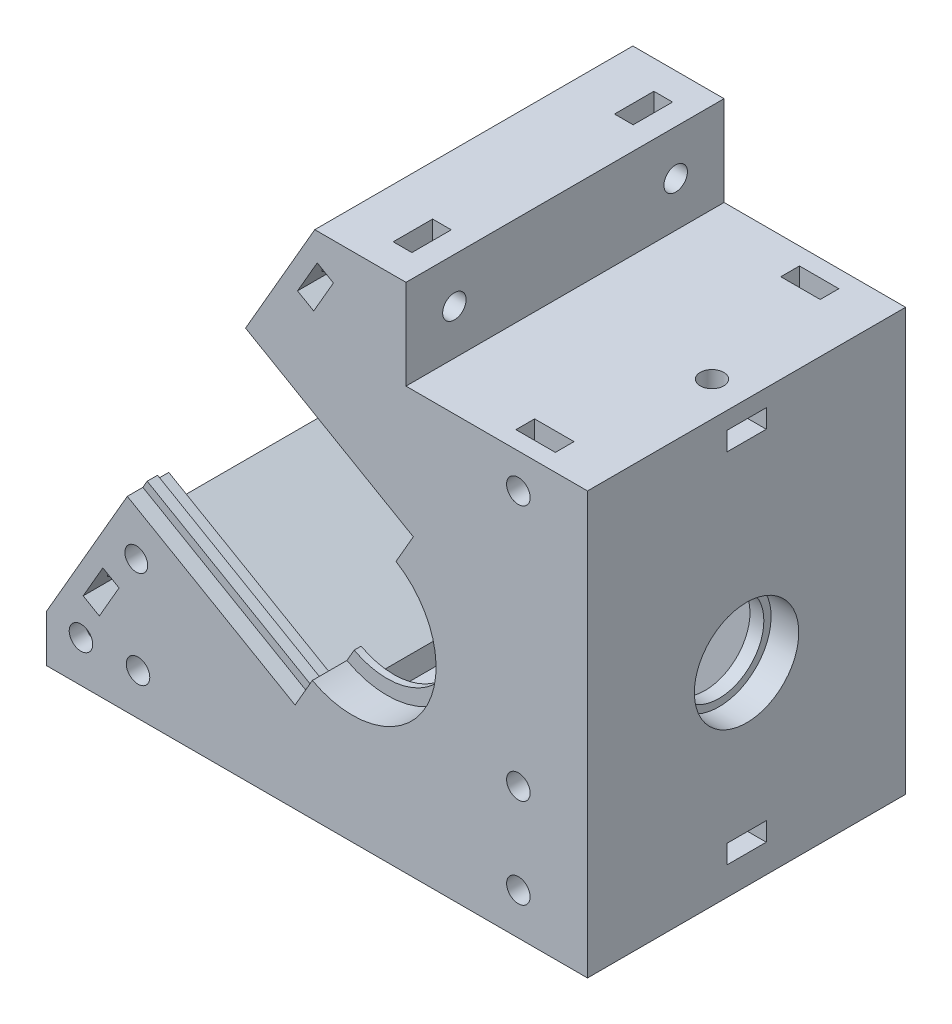
SolidWorks part; units mm, degrees
material "ABS"
ref_plane "Front Plane" through (0, 0, 0) normal (0, 0, 1) x (1, 0, 0)
ref_plane "Top Plane" through (0, 0, 0) normal (0, 1, 0) x (1, 0, 0)
ref_plane "Right Plane" through (0, 0, 0) normal (1, 0, 0) x (0, 0, -1)
sketch "Sketch1" plane through (0, 0, 0) normal (0, 0, 1) x (1, 0, 0)
  line L0 (-14, -24.2487) -> (-38, -10.3923)
  line L1 (-38, 33) -> (34, 33)
  line L2 (-38, 33) -> (-38, -31)
  line L3 (-38, -31) -> (34, -31)
  line L4 (34, 33) -> (34, -31)
  line L7 (-15, -31) -> (-15, -27.5)
  line L8 (-15, -27.5) -> (15, -27.5)
  line L9 (15, -27.5) -> (15, -31)
  line L16 (14, 24.2487) -> (-10, 38.1051)
  line L17 (7.75, 33) -> (7.75, 46)
  line L18 (7.75, 46) -> (-5.25, 46)
  line L19 (28, 10) -> (28, -10)
  line L20 (28, 10) -> (28, 14)
  line L21 (28, 14) -> (16.8, 22.4)
  line L22 (-38, -10.3923) -> (-5.4419, 46)
  line L23 (-5.4419, 46) -> (-5.25, 46)
  line L24 (-38, -10.3923) -> (-44.25, -21.2176)
  line L25 (-44.25, -21.2176) -> (-44.25, -31)
  line L26 (-44.25, -31) -> (-38, -31)
  line L27 (-44.25, -21.2176) -> (-44.25, -15.2176) construction
  line L28 (-44.25, -15.2176) -> (-8.906, 46) construction
  line L29 (-8.906, 46) -> (-5.4419, 46) construction
  line L30 (-10, 38.1051) -> (-12.5981, 39.6051) construction
  line L31 (-38, -10.3923) -> (-40.5981, -8.8923) construction
  line L32 (28, -10) -> (28, -14)
  line L33 (28, -14) -> (16.8, -22.4)
  circle A0 centre (0, 0) radius 28
  circle A1 centre (0, 0) radius 12.1
  circle A2 centre (0, 0) radius 10
  point P22 (28, 0)
  dimension "D1" = 56
  dimension "D2" = 24.2
  dimension "D3" = 20
  dimension "D4" = 34
  dimension "D6" = 3.5
  dimension "D7" = 15
  dimension "D8" = 15
  dimension "D10" = 38
  dimension "D5" = 33
  dimension "D9" = 31
  dimension "D11" = 30
  dimension "D12" = 7.75
  dimension "D13" = 13
  dimension "D14" = 13
  dimension "D15" = 20
  dimension "D16" = 9.1162
  dimension "D17" = 12.5
  dimension "D18" = 3
  dimension "D19" = 7.3038
  dimension "D20" = 7.3842
  dimension "D21" = 4
  dimension "D22" = 4
extrude "Boss-Extrude1" add sketch "Sketch1" along normal blind 6 contours A0 L20 L19 L8 L9 L3 L4 L1 L16 | A0 L0 L2 L3 L7 L8 | L25 L26 L2 L24 | L23 L22 L16 L1 L17 L18 | A0 L22 L0 | L22 A0 L8 A1 | A0 L16 L1 L22 | L22 L1 L16 | A0 L19 L20 | A0 L19 region at (-27.5845, -23.6186, 0) region at (-29.6112, -8.3492, 0) region at (-25.7125, -8.9071, 0) region at (-40.7539, -23.0811, 0) region at (-7.4692, 28.6958, 0) region at (11.6201, -26.2754, 0) region at (-8.035, 34.7017, 0) region at (25.6746, -12.8373, 0) region at (0.2743, 39.7035, 0) region at (25.6746, 12.8373, 0)
extrude "Boss-Extrude2" add sketch "Sketch1<3>" along normal blind 40 contours A0 L20 L19 L8 L9 L3 L4 L1 L16 | L23 L22 L16 L1 L17 L18 | A0 L0 L2 L3 L7 L8 | L25 L26 L2 L24 region at (-27.5845, -23.6186, 0) region at (-40.7539, -23.0811, 0) region at (11.6201, -26.2754, 0) region at (0.2743, 39.7035, 0)
sketch "Sketch1<3>" plane through (0, 0, 0) normal (0, 0, 1) x (1, 0, 0) same geometry as "Sketch1"
extrude "Boss-Extrude3" add sketch "Sketch1<4>" along normal blind 6 from surface contours A0 L20 L19 L8 L9 L3 L4 L1 L16 | L22 A0 L8 A1 | A0 L19 L20 | A0 L19 | A0 L0 L2 L3 L7 L8 | A0 L22 L0 | A0 L16 L1 L22 | L22 L1 L16 | L23 L22 L16 L1 L17 L18 | L25 L26 L2 L24 region at (-27.5845, -23.6186, 0) region at (-29.6112, -8.3492, 0) region at (-25.7125, -8.9071, 0) region at (-40.7539, -23.0811, 0) region at (-7.4692, 28.6958, 0) region at (11.6201, -26.2754, 0) region at (-8.035, 34.7017, 0) region at (25.6746, -12.8373, 0) region at (0.2743, 39.7035, 0) region at (25.6746, 12.8373, 0) starting at face at (14.8032, 7.3384, 40)
sketch "Sketch1<4>" plane through (0, 0, 0) normal (0, 0, 1) x (1, 0, 0) same geometry as "Sketch1"
extrude "Boss-Extrude4" add sketch "Sketch1<5>" against normal blind 1 from surface contours A1 A2 region at (-11.7578, 0, 0) starting at face at (4.1782, -2.8269, 6)
sketch "Sketch1<5>" plane through (0, 0, 0) normal (0, 0, 1) x (1, 0, 0) same geometry as "Sketch1"
extrude "Boss-Extrude5" add sketch "Sketch1<6>" along normal blind 1 from surface contours A1 A2 region at (-11.7578, 0, 0) starting at face at (4.1782, -2.8269, 40)
sketch "Sketch1<6>" plane through (0, 0, 0) normal (0, 0, 1) x (1, 0, 0) same geometry as "Sketch1"
sketch "Sketch2" plane through (0, -27.5, 0) normal (0, -1, 0) x (1, 0, 0)
  line L0 (15, 46) -> (15, 0) construction
  line L1 (15, 40) -> (-15, 40)
  line L2 (15, 40) -> (15, 6)
  line L3 (15, 6) -> (-15, 6)
  line L4 (-15, 40) -> (-15, 6)
  line L5 (-15, 46) -> (-15, 0) construction
  line L6 (-5.2678, 6) -> (5.2678, 6) construction
  line L7 (5.2678, 40) -> (-5.2678, 40) construction
sketch "Sketch3" plane through (0, 0, 0) normal (0, 0, -1) x (-1, 0, 0)
  line L0 (-6.05, 10.4789) -> (17.95, 24.3353)
  line L1 (44.25, -21.2176) -> (5.4419, 46) construction
  line L2 (6.05, -10.4789) -> (30.05, 3.3775)
  line L3 (-8.55, 14.809) -> (15.45, 28.6654)
  line L4 (8.2902, -14.959) -> (32.55, -0.9526)
  line L5 (6.05, -10.4789) -> (30.05, 3.3775) construction
  line L6 (-8.55, 14.809) -> (-6.05, 10.4789)
  line L7 (8.55, -14.809) -> (6.05, -10.4789)
  line L8 (-6.05, 10.4789) -> (6.05, -10.4789)
  line L9 (-8.55, 14.809) -> (-8.8098, 14.659)
  line L10 (-8.8098, 14.659) -> (8.2902, -14.959)
  line L11 (8.55, -14.809) -> (32.55, -0.9526) construction
  circle A0 centre (0, 0) radius 12.1 construction
  line M11 (44.25, -21.2176) -> (5.4419, 46)
  circle M17 centre (0, 0) radius 12.1
  dimension "D1" = 90
  dimension "D2" = 90
  dimension "D5" = 90
  dimension "D6" = 0.3
  dimension "D7" = 27.7128
  dimension "D3" = 5
  dimension "D4" = 5
extrude "Cut-Extrude1" cut sketch "Sketch2" against normal blind 10
extrude "Cut-Extrude2" cut sketch "Sketch3" against normal blind 49 contours L3 L6 L0 M11 | L2 L0 M17 M11 | L8 M17 | L9 L10 L6 M17 | L10 L8 M17 | L7 L4 L2 M11 | L10 L4 L7 M17 region at (-4.7, 19.5722, 0) region at (7.4296, 12.5684, 0) region at (-4.4474, 2.5677, 0) region at (-15.9416, 9.2039, 0) region at (0.1299, -0.075, 0) region at (-19.3, -5.7158, 0) region at (-7.1698, -12.7184, 0)
sketch "Sketch4" plane through (0.2598, -0.15, 0) normal (-0.866, 0.5, 0) x (0, 0, 1)
  line L0 (6, 17.1) -> (0, 17.1) construction
  line L1 (2.25, 17.1) -> (3.75, 17.1)
  line L2 (2.25, 17.1) -> (2.25, 15.85)
  line L3 (2.25, 15.85) -> (3.75, 15.85)
  line L4 (3.75, 17.1) -> (3.75, 15.85)
  line L5 (42.25, 17.1) -> (43.75, 17.1)
  line L6 (42.25, 17.1) -> (42.25, 15.85)
  line L7 (42.25, 15.85) -> (43.75, 15.85)
  line L8 (43.75, 17.1) -> (43.75, 15.85)
  line L9 (46, 17.1) -> (40, 17.1) construction
  line L10 (2.25, -15.85) -> (3.75, -15.85)
  line L11 (2.25, -15.85) -> (2.25, -17.1)
  line L12 (2.25, -17.1) -> (3.75, -17.1)
  line L13 (3.75, -15.85) -> (3.75, -17.1)
  line L14 (42.25, -15.85) -> (43.75, -15.85)
  line L15 (42.25, -15.85) -> (42.25, -17.1)
  line L16 (42.25, -17.1) -> (43.75, -17.1)
  line L17 (43.75, -15.85) -> (43.75, -17.1)
  line L18 (6, -17.1) -> (0, -17.1) construction
  line L19 (46, -17.1) -> (40, -17.1) construction
  point P6 (3, 17.1)
  point P7 (3, 17.1)
  point P12 (43, 17.1)
  point P15 (43, 17.1)
  point P28 (3, -17.1)
  point P29 (3, -17.1)
  point P30 (43, -17.1)
  point P33 (43, -17.1)
  dimension "D1" = 1.5
  dimension "D2" = 1.25
  dimension "D3" = 1.5
  dimension "D4" = 1.25
  dimension "D5" = 1.5
  dimension "D6" = 1.25
  dimension "D7" = 1.5
  dimension "D8" = 1.25
extrude "Boss-Extrude6" add sketch "Sketch4" along normal up to surface (28.0128 mm away) up to face at (-11.5855, 35.359, 23)
sketch "Sketch5" plane through (28, 0, 0) normal (-1, 0, 0) x (0, 0, 1)
  line L0 (40, 14) -> (6, -14) construction
  circle A0 centre (23, 0) radius 7.55
  circle A1 centre (23, 0) radius 6.5
  point P7 (23, 0)
  dimension "D1" = 15.1
  dimension "D2" = 13
extrude "Cut-Extrude3" cut sketch "Sketch5" against normal blind 49 contours A1 L0 | L0 A1 region at (28, -2.1295, 24.7537) region at (28, 2.1295, 21.2463)
extrude "Cut-Extrude4" cut sketch "Sketch5<3>" along normal blind 4 from surface contours L0 A0 A1 | A0 L0 A1 region at (28, 2.4881, 29.9351) region at (28, 4.6064, 28.3071) starting at face at (34, 6.5, 23)
sketch "Sketch5<3>" plane through (28, 0, 0) normal (-1, 0, 0) x (0, 0, 1) same geometry as "Sketch5"
sketch "Sketch6" plane through (-24, 13.8564, 0) normal (-0.866, 0.5, 0) x (0, 0, 1)
  line L0 (40, -28) -> (6, -28) construction
  line L1 (0, -40.5) -> (0, -17.1) construction
  line L2 (46, -17.1) -> (46, -40.5) construction
  line L3 (40, 28) -> (6, 28) construction
  line L5 (46, -40.5) -> (0, -40.5) construction
  circle A0 centre (4, -31) radius 1.7
  circle A1 centre (42, -31) radius 1.7
  circle A2 centre (42, 31) radius 1.7
  circle A3 centre (4, 31) radius 1.7
  dimension "D1" = 3.4
  dimension "D2" = 3.4
  dimension "D3" = 3.4
  dimension "D4" = 3.4
  dimension "D5" = 3
  dimension "D6" = 4
  dimension "D7" = 4
  dimension "D8" = 3
  dimension "D9" = 9.5
  dimension "D10" = 62
  dimension "D11" = 38
extrude "Cut-Extrude5" cut sketch "Sketch6" against normal blind 8
sketch "Sketch7" plane through (0, 0, 46) normal (0, 0, 1) x (1, 0, 0)
  line L0 (34, -31) -> (34, 33) construction
  line L1 (-44.25, -31) -> (34, -31)
  line L2 (-44.25, -31) -> (-44.25, -27)
  line L3 (-44.25, -27) -> (34, -27)
  line L4 (34, -31) -> (34, -27)
  line L6 (15, -27.5) -> (-15, -27.5) construction
  dimension "D1" = 0.5
extrude "Cut-Extrude6" cut sketch "Sketch7" against normal blind 64
sketch "Sketch8" plane through (0, 0, 46) normal (0, 0, 1) x (1, 0, 0)
  line L0 (34, -27) -> (-44.25, -27) construction
  line L1 (-44.25, -27) -> (-44.25, -21.2176) construction
  line L2 (34, -27) -> (34, 33) construction
  circle A0 centre (-39.25, -22) radius 1.7
  circle A1 centre (29, -22) radius 1.7
  dimension "D1" = 3.4
  dimension "D2" = 3.4
  dimension "D3" = 5
  dimension "D4" = 5
  dimension "D5" = 5
  dimension "D6" = 5
extrude "Cut-Extrude7" cut sketch "Sketch8" against normal blind 10 contours A0 region at (-39.25, -22, 46)
extrude "Cut-Extrude9" cut sketch "Sketch8<2>" along normal blind 10 from surface contours A0 region at (-39.25, -22, 46) starting at face at (-3.6295, 7.9996, 0)
sketch "Sketch8<2>" plane through (0, 0, 46) normal (0, 0, 1) x (1, 0, 0) same geometry as "Sketch8"
sketch "Sketch10" plane through (-44.25, 0, 0) normal (-1, 0, 0) x (0, 0, 1)
  line L0 (0, -27) -> (46, -27) construction
  line L1 (20.15, -21.2176) -> (25.85, -21.2176)
  line L2 (20.15, -21.2176) -> (20.15, -23.9176)
  line L3 (20.15, -23.9176) -> (25.85, -23.9176)
  line L4 (25.85, -21.2176) -> (25.85, -23.9176)
  line L5 (20.15, -21.2176) -> (25.85, -23.9176) construction
  line L6 (20.15, -23.9176) -> (25.85, -21.2176) construction
  line L7 (46, -21.2176) -> (0, -21.2176) construction
  point P0 (23, -22.5676)
  point P8 (23, -27)
  dimension "D1" = 5.7
  dimension "D2" = 2.7
extrude "Cut-Extrude10" cut sketch "Sketch10" against normal blind 8.5
sketch "Sketch11" plane through (34, 0, 0) normal (1, 0, 0) x (0, 0, -1)
  line L0 (0, -27) -> (-46, -27) construction
  line L1 (-43.7, -24.85) -> (-41, -24.85)
  line L2 (-43.7, -24.85) -> (-43.7, -19.15)
  line L3 (-43.7, -19.15) -> (-41, -19.15)
  line L4 (-41, -24.85) -> (-41, -19.15)
  line L5 (-43.7, -24.85) -> (-41, -19.15) construction
  line L6 (-43.7, -19.15) -> (-41, -24.85) construction
  line L7 (-46, -27) -> (-46, 33) construction
  line L8 (-5, -24.85) -> (-2.5, -24.85)
  line L9 (-5, -24.85) -> (-5, -19.15)
  line L10 (-5, -19.15) -> (-2.5, -19.15)
  line L11 (-2.5, -24.85) -> (-2.5, -19.15)
  line L12 (-5, -24.85) -> (-2.5, -19.15) construction
  line L13 (-5, -19.15) -> (-2.5, -24.85) construction
  line L14 (0, 33) -> (0, -27) construction
  point P0 (-42.35, -22)
  point P9 (-3.75, -22)
  dimension "D1" = 5.7
  dimension "D2" = 2.7
  dimension "D3" = 5
  dimension "D4" = 5
  dimension "D5" = 5.7
  dimension "D6" = 2.5
  dimension "D7" = 5
extrude "Cut-Extrude12" cut sketch "Sketch11" along normal blind 8.5 from surface starting at face at (-44.25, -23.3382, 23)
extrude "Cut-Extrude13" cut sketch "Sketch10<2>" along normal blind 8.5 from surface starting at face at (34, 3, 23)
sketch "Sketch10<2>" plane through (-44.25, 0, 0) normal (-1, 0, 0) x (0, 0, 1) same geometry as "Sketch10"
sketch "Sketch12" plane through (0, 0, 46) normal (0, 0, 1) x (1, 0, 0)
  line L0 (-36.0831, -11.6722) -> (-38.9331, -16.6086)
  line L1 (-38.9331, -16.6086) -> (-36.5949, -17.9586)
  line L2 (-36.5949, -17.9586) -> (-33.7449, -13.0222)
  line L3 (-33.7449, -13.0222) -> (-36.0831, -11.6722)
  line L4 (-32.55, -0.9526) -> (-44.25, -21.2176) construction
  line L6 (-39.5, -12.9904) -> (-28.0908, -19.5775) construction
  line L7 (-5.0831, 42.0214) -> (-7.9331, 37.085)
  line L8 (-7.9331, 37.085) -> (-5.5949, 35.735)
  line L9 (-5.5949, 35.735) -> (-2.7449, 40.6714)
  line L10 (-2.7449, 40.6714) -> (-5.0831, 42.0214)
  point P6 (-37.5081, -14.1404)
  point P7 (-39.5, -12.9904)
  point P17 (-8.7952, 39.4691)
  dimension "D1" = 2.7
  dimension "D2" = 5.7
  dimension "D3" = 5
  dimension "D4" = 9.5
  dimension "D5" = 90
  dimension "D6" = 2.7
  dimension "D7" = 5.7
  dimension "D8" = 62
extrude "Cut-Extrude14" cut sketch "Sketch12" against normal blind 7.5
extrude "Cut-Extrude15" cut sketch "Sketch12<2>" along normal blind 7.5 from surface starting at face at (-37.55, -22, 0)
sketch "Sketch12<2>" plane through (0, 0, 46) normal (0, 0, 1) x (1, 0, 0) same geometry as "Sketch12"
sketch "Sketch13" plane through (7.75, 0, 0) normal (1, 0, 0) x (0, 0, -1)
  line L0 (-46, 46) -> (0, 46) construction
  line L1 (-46, 46) -> (0, 33) construction
  circle A0 centre (-39, 39.5) radius 1.7
  circle A1 centre (-7, 39.5) radius 1.7
  point P10 (-23, 39.5)
  dimension "D1" = 3.4
  dimension "D2" = 3.4
  dimension "D3" = 6.5
  dimension "D4" = 16
  dimension "D5" = 16
extrude "Cut-Extrude16" cut sketch "Sketch13" against normal blind 10
sketch "Sketch14" plane through (0, 46, 0) normal (0, 1, 0) x (1, 0, 0)
  line L0 (1.75, -9.85) -> (4.45, -9.85)
  line L1 (1.75, -41.85) -> (4.45, -41.85)
  line L2 (1.75, -41.85) -> (1.75, -36.15)
  line L3 (1.75, -36.15) -> (4.45, -36.15)
  line L4 (4.45, -41.85) -> (4.45, -36.15)
  line L5 (1.75, -41.85) -> (4.45, -36.15) construction
  line L6 (1.75, -36.15) -> (4.45, -41.85) construction
  line L7 (1.75, -9.85) -> (1.75, -4.15)
  line L8 (1.75, -4.15) -> (4.45, -4.15)
  line L9 (4.45, -9.85) -> (4.45, -4.15)
  line L10 (1.75, -9.85) -> (4.45, -4.15) construction
  line L11 (1.75, -4.15) -> (4.45, -9.85) construction
  line L12 (7.75, -46) -> (7.75, 0) construction
  point P0 (3.1, -39)
  point P5 (3.1, -7)
  point P13 (7.75, -23)
  dimension "D1" = 2.7
  dimension "D2" = 5.7
  dimension "D3" = 2.7
  dimension "D4" = 5.7
  dimension "D5" = 6
  dimension "D6" = 16
  dimension "D7" = 16
extrude "Cut-Extrude17" cut sketch "Sketch14" against normal blind 10
sketch "Sketch15" plane through (0, 0, 46) normal (0, 0, 1) x (1, 0, 0)
  line L0 (0, 30.9475) -> (0, -37.7326) construction
  line L1 (0, 0) -> (-6.3411, -23.6652) construction
  line L2 (34, -27) -> (-44.25, -27) construction
  line L3 (0, 0) -> (6.3411, 23.6652) construction
  line L4 (34, 33) -> (7.75, 33) construction
  line L5 (-6.3411, -23.6652) -> (-16.7248, -20.8829) construction
  line L6 (-6.3411, -23.6652) -> (4.0426, -26.4475) construction
  line L7 (-16.7248, -20.8829) -> (-24.6937, -18.7476) construction
  line L8 (-24.6937, -18.7476) -> (-2.694, 63.3561) construction
  dimension "D1" = 15
  dimension "D2" = 24.5
  dimension "D3" = 44.25
  dimension "D4" = 34
  dimension "D5" = 27
  dimension "D6" = 15
  dimension "D7" = 24.5
  dimension "D8" = 1.4089
  dimension "D9" = 9.3348
  dimension "D10" = 40.3411
  dimension "D11" = 3.3348
  dimension "D12" = 10.75
  dimension "D13" = 10.75
  dimension "D14" = 8.25
  dimension "D15" = 85
  dimension "D16" = 17.3561
  dimension "D17" = 10.444
  dimension "D18" = 14.5802
sketch "Sketch17" plane through (0, 0, 46) normal (0, 0, 1) x (1, 0, 0)
  line L0 (34, -27) -> (-44.25, -27) construction
  circle A0 centre (-31, -22) radius 1.7
  circle A1 centre (24, -22) radius 1.7
  dimension "D2" = 3.4
  dimension "D3" = 3.4
  dimension "D1" = 5
  dimension "D4" = 31
  dimension "D5" = 24
extrude "Cut-Extrude19" cut sketch "Sketch17" against normal blind 20
extrude "Cut-Extrude20" cut sketch "Sketch17<2>" along normal blind 20 from surface starting at face at (-5.339, 38.8782, 0)
sketch "Sketch17<2>" plane through (0, 0, 46) normal (0, 0, 1) x (1, 0, 0) same geometry as "Sketch17"
sketch "Sketch19" plane through (0, -27, 0) normal (0, -1, 0) x (1, 0, 0)
  line L1 (-44.25, 46) -> (34, 46)
  line L2 (-44.25, 46) -> (-44.25, 0)
  line L3 (-44.25, 0) -> (34, 0)
  line L4 (34, 46) -> (34, 0)
extrude "Boss-Extrude7" add sketch "Sketch19" along normal blind 1
sketch "Sketch9" plane through (0, -28, 0) normal (0, -1, 0) x (1, 0, 0)
  line L1 (-44.25, 46) -> (34, 0) construction
  line L3 (-44.25, 46) -> (-44.25, 0) construction
  line L4 (34, 0) -> (34, 46) construction
  circle A0 centre (-39.25, 23) radius 1.7
  circle A1 centre (29, 23) radius 1.7
  point P10 (-5.125, 23)
  dimension "D1" = 3.4
  dimension "D2" = 3.4
  dimension "D3" = 5
  dimension "D4" = 5
  dimension "D5" = 68.25
extrude "Cut-Extrude8" cut sketch "Sketch9" against normal blind 10
sketch "Sketch20" plane through (34, 0, 0) normal (1, 0, 0) x (0, 0, -1)
  line L0 (0, -28) -> (-46, -28) construction
  circle A0 centre (-29, -13) radius 1.7
  circle A1 centre (-17, -13) radius 1.7
  circle A2 centre (-23, 0) radius 7.55 construction
  dimension "D1" = 3.4
  dimension "D2" = 3.4
  dimension "D3" = 15
  dimension "D4" = 6
  dimension "D5" = 12
sketch "Sketch22" plane through (0, -28, 0) normal (0, -1, 0) x (1, 0, 0)
  line L1 (26.85, 2.5) -> (21.15, 2.5)
  line L2 (26.85, 2.5) -> (26.85, 5.2)
  line L3 (26.85, 5.2) -> (21.15, 5.2)
  line L4 (21.15, 2.5) -> (21.15, 5.2)
  line L5 (26.85, 2.5) -> (21.15, 5.2) construction
  line L6 (26.85, 5.2) -> (21.15, 2.5) construction
  line L7 (34, 0) -> (34, 46) construction
  line L8 (-44.25, 0) -> (34, 0) construction
  line L12 (-28.15, 2.5) -> (-33.85, 2.5)
  line L13 (-28.15, 2.5) -> (-28.15, 5.2)
  line L14 (-28.15, 5.2) -> (-33.85, 5.2)
  line L15 (-33.85, 2.5) -> (-33.85, 5.2)
  line L16 (-28.15, 2.5) -> (-33.85, 5.2) construction
  line L17 (-28.15, 5.2) -> (-33.85, 2.5) construction
  line L18 (-28.15, 40.8) -> (-33.85, 40.8)
  line L19 (-28.15, 40.8) -> (-28.15, 43.5)
  line L20 (-28.15, 43.5) -> (-33.85, 43.5)
  line L21 (-33.85, 40.8) -> (-33.85, 43.5)
  line L22 (-28.15, 40.8) -> (-33.85, 43.5) construction
  line L23 (-28.15, 43.5) -> (-33.85, 40.8) construction
  line L24 (26.85, 40.8) -> (21.15, 40.8)
  line L25 (26.85, 40.8) -> (26.85, 43.5)
  line L26 (26.85, 43.5) -> (21.15, 43.5)
  line L27 (21.15, 40.8) -> (21.15, 43.5)
  line L28 (26.85, 40.8) -> (21.15, 43.5) construction
  line L29 (26.85, 43.5) -> (21.15, 40.8) construction
  line L30 (34, 46) -> (-44.25, 46) construction
  point P0 (24, 3.85)
  point P9 (-31, 3.85)
  point P14 (-31, 42.15)
  point P19 (24, 42.15)
  dimension "D3" = 2.7
  dimension "D4" = 5.7
  dimension "D1" = 10
  dimension "D2" = 2.5
  dimension "D5" = 2.7
  dimension "D6" = 5.7
  dimension "D7" = 2.7
  dimension "D8" = 5.7
  dimension "D9" = 2.7
  dimension "D10" = 5.7
  dimension "D11" = 55
  dimension "D12" = 2.5
extrude "Cut-Extrude22" cut sketch "Sketch22" against normal blind 9.5
sketch "Sketch23" plane through (0, 0, 46) normal (0, 0, 1) x (1, 0, 0)
  line L0 (34, -28) -> (34, 33) construction
  line L1 (34, 33) -> (7.75, 33) construction
  circle A0 centre (24, 28) radius 1.7
  circle A1 centre (24, -9) radius 1.7
  dimension "D1" = 3.4
  dimension "D4" = 3.4
  dimension "D2" = 10
  dimension "D3" = 5
  dimension "D5" = 37
sketch "Sketch24" plane through (0, 33, 0) normal (0, 1, 0) x (1, 0, 0)
  line L0 (34, -46) -> (7.75, -46) construction
  line L1 (21.15, -40.8) -> (26.85, -40.8)
  line L2 (21.15, -40.8) -> (21.15, -43.5)
  line L3 (21.15, -43.5) -> (26.85, -43.5)
  line L4 (26.85, -40.8) -> (26.85, -43.5)
  line L5 (21.15, -40.8) -> (26.85, -43.5) construction
  line L6 (21.15, -43.5) -> (26.85, -40.8) construction
  line L7 (34, -46) -> (34, 0) construction
  line L8 (21.15, -2.5) -> (26.85, -2.5)
  line L9 (21.15, -2.5) -> (21.15, -5.2)
  line L10 (21.15, -5.2) -> (26.85, -5.2)
  line L11 (26.85, -2.5) -> (26.85, -5.2)
  line L12 (21.15, -2.5) -> (26.85, -5.2) construction
  line L13 (21.15, -5.2) -> (26.85, -2.5) construction
  line L14 (7.75, 0) -> (34, 0) construction
  circle A0 centre (29, -23) radius 1.7
  point P0 (24, -42.15)
  point P9 (24, -3.85)
  point P19 (34, -23)
  dimension "D1" = 2.7
  dimension "D2" = 5.7
  dimension "D5" = 2.7
  dimension "D6" = 5.7
  dimension "D8" = 3.4
  dimension "D3" = 2.5
  dimension "D4" = 10
  dimension "D7" = 2.5
  dimension "D9" = 5
extrude "Cut-Extrude23" cut sketch "Sketch23" against normal blind 12
extrude "Cut-Extrude24" cut sketch "Sketch23<2>" along normal blind 12 from surface starting at face at (-29.3, -22, 0)
sketch "Sketch23<2>" plane through (0, 0, 46) normal (0, 0, 1) x (1, 0, 0) same geometry as "Sketch23"
extrude "Cut-Extrude25" cut sketch "Sketch24" against normal blind 8.5
sketch "Sketch26" plane through (34, 0, 0) normal (1, 0, 0) x (0, 0, -1)
  line L0 (-46, 33) -> (0, 33) construction
  line L1 (-25.85, 30.5) -> (-20.15, 30.5)
  line L2 (-25.85, 30.5) -> (-25.85, 27.8)
  line L3 (-25.85, 27.8) -> (-20.15, 27.8)
  line L4 (-20.15, 30.5) -> (-20.15, 27.8)
  line L5 (-25.85, 30.5) -> (-20.15, 27.8) construction
  line L6 (-25.85, 27.8) -> (-20.15, 30.5) construction
  point P0 (-23, 29.15)
  point P8 (-23, 33)
  dimension "D1" = 5.7
  dimension "D2" = 2.7
  dimension "D3" = 2.5
extrude "Cut-Extrude27" cut sketch "Sketch26" against normal blind 8.5
sketch "Sketch27" plane through (0, 0, 6) normal (0, 0, 1) x (1, 0, 0)
  line L1 (24, -12.2909) -> (26.85, -10.6454)
  line L2 (26.85, -10.6454) -> (26.85, -7.3546)
  line L3 (26.85, -7.3546) -> (24, -5.7091)
  line L4 (24, -5.7091) -> (21.15, -7.3546)
  line L5 (21.15, -7.3546) -> (21.15, -10.6454)
  line L6 (21.15, -10.6454) -> (24, -12.2909)
  circle A0 centre (24, -9) radius 2.85 construction
  dimension "D1" = 5.7
extrude "Cut-Extrude28" cut sketch "Sketch27" against normal blind 3
extrude "Cut-Extrude29" cut sketch "Sketch27<2>" along normal blind 3 from surface starting at face at (25.7, -9, 40)
sketch "Sketch27<2>" plane through (0, 0, 6) normal (0, 0, 1) x (1, 0, 0) same geometry as "Sketch27"
sketch "Sketch28" plane through (34, 0, 0) normal (1, 0, 0) x (0, 0, -1)
  circle A0 centre (-23, 0) radius 18 construction
  dimension "D1" = 36
sketch "Sketch29" plane through (34, 0, 0) normal (1, 0, 0) x (0, 0, -1)
  circle A0 centre (-39, 28) radius 1.65
  circle A1 centre (-7, 28) radius 1.65
  circle A2 centre (-42, -23) radius 1.65
  circle A3 centre (-4, -23) radius 1.65
  dimension "D1" = 3.3
  dimension "D2" = 16
  dimension "D3" = 16
  dimension "D4" = 28
  dimension "D5" = 23
  dimension "D6" = 19
  dimension "D7" = 19
extrude "Cut-Extrude30" [suppressed] cut sketch "Sketch29" against normal blind 15
sketch "Sketch30" plane through (0, 33, 0) normal (0, 1, 0) x (1, 0, 0)
  line L0 (34, -46) -> (34, 0) construction
  line L1 (29.3, -9.85) -> (32, -9.85)
  line L2 (29.3, -9.85) -> (29.3, -4.15)
  line L3 (29.3, -4.15) -> (32, -4.15)
  line L4 (32, -9.85) -> (32, -4.15)
  line L5 (29.3, -9.85) -> (32, -4.15) construction
  line L6 (29.3, -4.15) -> (32, -9.85) construction
  line L7 (29.3, -41.85) -> (32, -41.85)
  line L8 (29.3, -41.85) -> (29.3, -36.15)
  line L9 (29.3, -36.15) -> (32, -36.15)
  line L10 (32, -41.85) -> (32, -36.15)
  line L11 (29.3, -41.85) -> (32, -36.15) construction
  line L12 (29.3, -36.15) -> (32, -41.85) construction
  point P0 (30.65, -7)
  point P5 (30.65, -39)
  point P12 (34, -23)
  dimension "D1" = 2.7
  dimension "D2" = 5.7
  dimension "D3" = 2.7
  dimension "D4" = 5.7
  dimension "D5" = 16
  dimension "D6" = 16
  dimension "D7" = 2
extrude "Cut-Extrude31" [suppressed] cut sketch "Sketch30" against normal blind 8.5
sketch "Sketch31" plane through (0, -28, 0) normal (0, -1, 0) x (1, 0, 0)
  line L0 (34, 0) -> (34, 46) construction
  line L1 (32, 44.85) -> (29.3, 44.85)
  line L2 (32, 44.85) -> (32, 39.15)
  line L3 (32, 39.15) -> (29.3, 39.15)
  line L4 (29.3, 44.85) -> (29.3, 39.15)
  line L5 (32, 44.85) -> (29.3, 39.15) construction
  line L6 (32, 39.15) -> (29.3, 44.85) construction
  line L7 (32, 6.85) -> (29.3, 6.85)
  line L8 (32, 6.85) -> (32, 1.15)
  line L9 (32, 1.15) -> (29.3, 1.15)
  line L10 (29.3, 6.85) -> (29.3, 1.15)
  line L11 (32, 6.85) -> (29.3, 1.15) construction
  line L12 (32, 1.15) -> (29.3, 6.85) construction
  point P0 (30.65, 42)
  point P5 (30.65, 4)
  point P13 (34, 23)
  dimension "D1" = 2
  dimension "D2" = 2.7
  dimension "D3" = 5.7
  dimension "D4" = 5.7
  dimension "D5" = 19
  dimension "D6" = 19
  dimension "D7" = 2.7
extrude "Cut-Extrude32" [suppressed] cut sketch "Sketch31" against normal blind 8.5
sketch "Sketch32" plane through (0, 0, 0) normal (0, 0, -1) x (-1, 0, 0)
  line L1 (31.25, -8.1436) -> (39.25, -22) construction
  line L2 (44.25, -21.2176) -> (32.55, -0.9526) construction
  circle A0 centre (31.25, -8.1436) radius 1.65
  dimension "D1" = 3.3
  dimension "D2" = 16
extrude "Cut-Extrude33" cut sketch "Sketch32" against normal blind 89
sketch "Sketch33" plane through (0, 0, 6) normal (0, 0, 1) x (1, 0, 0)
  line L0 (-32.55, -0.9526) -> (-8.2902, -14.959) construction
  line L1 (-34.075, -6.5126) -> (-34.075, -9.7746)
  line L2 (-34.075, -9.7746) -> (-31.25, -11.4056)
  line L3 (-31.25, -11.4056) -> (-28.425, -9.7746)
  line L4 (-28.425, -9.7746) -> (-28.425, -6.5126)
  line L5 (-28.425, -6.5126) -> (-31.25, -4.8816)
  line L6 (-31.25, -4.8816) -> (-34.075, -6.5126)
  circle A0 centre (-31.25, -8.1436) radius 2.825 construction
  dimension "D1" = 5.65
extrude "Cut-Extrude34" cut sketch "Sketch33" against normal blind 2.5
extrude "Cut-Extrude35" cut sketch "Sketch33<2>" along normal blind 2.5 from surface starting at face at (-29.6, -8.1436, 40)
sketch "Sketch33<2>" plane through (0, 0, 6) normal (0, 0, 1) x (1, 0, 0) same geometry as "Sketch33"
equation "\"D8@Sketch1\"=\"D7@Sketch1\""
equation "\"D4@Sketch4\"=\"D2@Sketch4\""
equation "\"D6@Sketch4\"=\"D2@Sketch4\""
equation "\"D8@Sketch4\"=\"D2@Sketch4\""
equation "\"D4@Sketch6\"=\"D3@Sketch6\""
equation "\"D2@Sketch6\"=\"D3@Sketch6\""
equation "\"D1@Sketch6\"=\"D3@Sketch6\""
equation "\"D2@Sketch13\"=\"D1@Sketch13\""
equation "\"D5@Sketch13\"=\"D4@Sketch13\""
equation "\"D3@Sketch17\"=\"D2@Sketch17\""
equation "\"D2@Sketch8\"=\"D1@Sketch8\""
equation "\"D1@Sketch14\"=\"D3@Sketch14\""
equation "\"D1@Sketch20\"=\"D2@Sketch20\""
equation "\"D9@Sketch22\"=\"D3@Sketch22\""
equation "\"D5@Sketch22\"=\"D3@Sketch22\""
equation "\"D7@Sketch22\"=\"D3@Sketch22\""
equation "\"D5@Sketch24\"=\"D1@Sketch24\""
